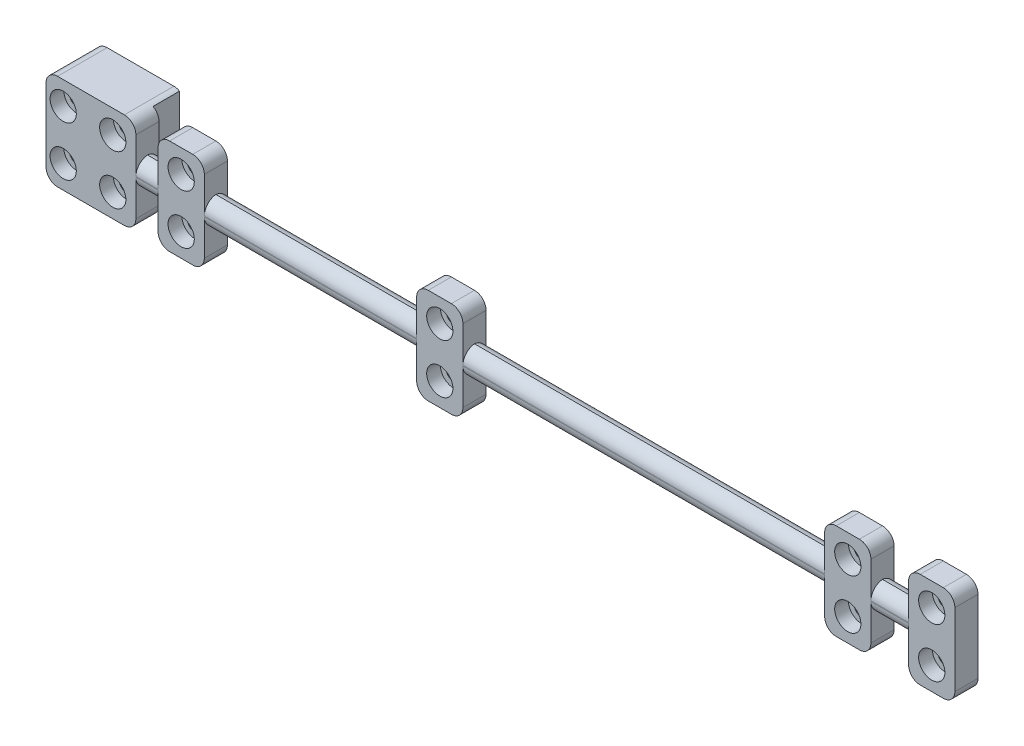
SolidWorks part; units mm, degrees
ref_plane "Front Plane" through (0, 0, 0) normal (0, 0, 1) x (1, 0, 0)
ref_plane "Top Plane" through (0, 0, 0) normal (0, 1, 0) x (1, 0, 0)
ref_plane "Right Plane" through (0, 0, 0) normal (1, 0, 0) x (0, 0, -1)
sketch "Sketch1" plane through (0, 0, 0) normal (0, 0, 1) x (1, 0, 0)
  line L1 (-12.7, -14.5) -> (12.7, -14.5)
  line L2 (-12.7, -14.5) -> (-12.7, 14.5)
  line L3 (-12.7, 14.5) -> (12.7, 14.5)
  line L4 (12.7, -14.5) -> (12.7, 14.5)
  line L5 (-12.7, -14.5) -> (12.7, 14.5) construction
  line L6 (-12.7, 14.5) -> (12.7, -14.5) construction
  line L7 (-7.5, 7.5) -> (7.5, 7.5) construction
  line L8 (-7.5, 7.5) -> (-7.5, -7.5) construction
  line L9 (-7.5, -7.5) -> (7.5, -7.5) construction
  line L10 (7.5, 7.5) -> (7.5, -7.5) construction
  line L11 (-7.5, 7.5) -> (7.5, -7.5) construction
  line L12 (-7.5, -7.5) -> (7.5, 7.5) construction
  point P0 (0, 0)
  point P6 (0, 0)
  dimension "D1" = 29
  dimension "D2" = 25.4
  dimension "D3" = 15
extrude "Boss-Extrude1" add sketch "Sketch1" along normal blind 8
sketch "Sketch2" plane through (0, 0, 8) normal (0, 0, 1) x (1, 0, 0)
  line L0 (12.7, 14.5) -> (-12.7, 14.5) construction
  line L1 (-12.7, -14.5) -> (262.3, -14.5)
  line L2 (-12.7, -14.5) -> (-12.7, 14.5)
  line L3 (-12.7, 14.5) -> (262.3, 14.5)
  line L4 (262.3, -14.5) -> (262.3, 14.5)
  dimension "D1" = 275
extrude "Boss-Extrude2" add sketch "Sketch2" along normal blind 7
sketch "Sketch3" plane through (0, 0, 15) normal (0, 0, 1) x (1, 0, 0)
  line L0 (7.5, 0) -> (28.2, 0) construction
  line L1 (-7.5, 7.5) -> (7.5, 7.5) construction
  line L2 (-7.5, 7.5) -> (-7.5, -7.5) construction
  line L3 (-7.5, -7.5) -> (7.5, -7.5) construction
  line L4 (7.5, 7.5) -> (7.5, -7.5) construction
  line L5 (-7.5, 7.5) -> (7.5, -7.5) construction
  line L6 (-7.5, -7.5) -> (7.5, 7.5) construction
  line L7 (28.2, 0) -> (106.45, 0) construction
  line L8 (28.2, 0) -> (28.2, -7.5) construction
  line L9 (28.2, 0) -> (28.2, 7.5) construction
  line L10 (106.45, 7.5) -> (106.45, 0) construction
  line L11 (106.45, 0) -> (106.45, -7.5) construction
  line L12 (106.45, 0) -> (229.9, 0) construction
  line L13 (229.9, 0) -> (255.3, 0) construction
  line L14 (229.9, 7.5) -> (229.9, 0) construction
  line L15 (229.9, 0) -> (229.9, -7.5) construction
  line L16 (255.3, 7.5) -> (255.3, 0) construction
  line L17 (255.3, 0) -> (255.3, -7.5) construction
  line L18 (255.3, 0) -> (262.3, 0) construction
  line L19 (262.3, -14.5) -> (262.3, 14.5) construction
  point P0 (0, 0)
  point P7 (-7.5, 7.5)
  point P8 (-7.5, -7.5)
  point P9 (7.5, -7.5)
  point P10 (7.5, 7.5)
  point P18 (28.2, -7.5)
  point P19 (28.2, 7.5)
  point P20 (106.45, -7.5)
  point P21 (106.45, 7.5)
  point P28 (229.9, 7.5)
  point P29 (229.9, -7.5)
  point P30 (255.3, 7.5)
  point P31 (255.3, -7.5)
  dimension "D1" = 15
  dimension "D2" = 20.7
  dimension "D3" = 78.25
  dimension "D4" = 25.4
  dimension "D5" = 7
hole_wizard "CBORE for #8 Socket Head Cap Screw1" positions "3DSketch2" profile "Sketch4" counterbore size "#8" standard "ANSI Inch"
sketch3d "3DSketch2"
  point P0 (-7.5, 7.5, 15)
  point P3 (7.5, 7.5, 15)
  point P6 (7.5, -7.5, 15)
  point P9 (-7.5, -7.5, 15)
  point P12 (28.2, 7.5, 15)
  point P15 (28.2, -7.5, 15)
  point P18 (106.45, 7.5, 15)
  point P21 (106.45, -7.5, 15)
  point P24 (229.9, 7.5, 15)
  point P27 (229.9, -7.5, 15)
  point P30 (255.3, 7.5, 15)
  point P33 (255.3, -7.5, 15)
sketch "Sketch4" plane through (-7.5, 7.5, 15) normal (1, 0, 0) x (0, -1, 0)
  line L0 (0, 0) -> (0, 20)
  line L1 (0, 20) -> (2.2479, 18.6493)
  line L2 (2.2479, 18.6493) -> (2.2479, 4.1656)
  line L3 (2.2479, 4.1656) -> (3.9688, 4.1656)
  line L4 (3.9688, 4.1656) -> (3.9688, 0)
  line L5 (3.9688, 0) -> (0, 0)
  line L10 (0, 20) -> (-2.2479, 18.6493) construction
  line L11 (0, -6.35) -> (0, 107.95) construction
  dimension "Hole Dia." = 4.4958
  dimension "Hole Depth" = 20
  dimension "C'Bore Dia." = 7.9375
  dimension "C'Bore Depth" = 4.1656
  dimension "Drill Angle" = 118
sketch "Sketch5" plane through (0, 0, 15) normal (0, 0, 1) x (1, 0, 0)
  line L0 (262.3, 14.5) -> (-12.7, 14.5) construction
  line L1 (35.2, 14.5) -> (99.45, 14.5)
  line L2 (35.2, 14.5) -> (35.2, 4)
  line L3 (35.2, 4) -> (99.45, 4)
  line L4 (99.45, 14.5) -> (99.45, 4)
  line L5 (28.2, 7.5) -> (35.2, 7.5) construction
  line L6 (113.45, 14.5) -> (222.9, 14.5)
  line L7 (113.45, 14.5) -> (113.45, 4)
  line L8 (113.45, 4) -> (222.9, 4)
  line L9 (222.9, 14.5) -> (222.9, 4)
  line L10 (236.9, 14.5) -> (248.3, 14.5)
  line L11 (236.9, 14.5) -> (236.9, 4)
  line L12 (236.9, 4) -> (248.3, 4)
  line L13 (248.3, 14.5) -> (248.3, 4)
  line L14 (106.45, 7.5) -> (99.45, 7.5) construction
  line L15 (106.45, 7.5) -> (113.45, 7.5) construction
  line L16 (229.9, 7.5) -> (222.9, 7.5) construction
  line L17 (229.9, 7.5) -> (236.9, 7.5) construction
  line L18 (248.3, 7.5) -> (255.3, 7.5) construction
  line L19 (7.5, 7.5) -> (14.5, 7.5) construction
  line L20 (14.5, 14.5) -> (21.2, 14.5)
  line L21 (14.5, 14.5) -> (14.5, 4)
  line L22 (14.5, 4) -> (21.2, 4)
  line L23 (21.2, 14.5) -> (21.2, 4)
  line L24 (28.2, 7.5) -> (21.2, 7.5) construction
  line L25 (28.2, 0) -> (106.45, 0) construction
  dimension "D1" = 7
  dimension "D2" = 4
extrude "Cut-Extrude1" cut sketch "Sketch5" against normal blind 10
mirror "Mirror1" about plane through (0, 0, 0) normal (0, 1, 0) of "Cut-Extrude1"
fillet "Fillet1" radius 3.9 16 edges at (168.175, 4, 15) (242.6, 4, 15) (242.6, 4, 8) (242.6, -4, 15) (242.6, -4, 8) (168.175, -4, 8) (168.175, -4, 15) (168.175, 4, 8) (67.325, 4, 8) (67.325, 4, 15) (67.325, -4, 8) (67.325, -4, 15) (17.85, -4, 8) (17.85, -4, 15) (17.85, 4, 8) (17.85, 4, 15)
fillet "Fillet2" radius 3.5 20 edges at (248.3, 14.5, 11.5) (262.3, 14.5, 11.5) (262.3, -14.5, 11.5) (236.9, 14.5, 11.5) (248.3, -14.5, 11.5) (236.9, -14.5, 11.5) (222.9, -14.5, 11.5) (222.9, 14.5, 11.5) (99.45, 14.5, 11.5) (113.45, 14.5, 11.5) (113.45, -14.5, 11.5) (99.45, -14.5, 11.5) (21.2, -14.5, 11.5) (35.2, -14.5, 11.5) (21.2, 14.5, 11.5) (35.2, 14.5, 11.5) (14.5, 14.5, 11.5) (-12.7, 14.5, 7.5) (14.5, -14.5, 11.5) (-12.7, -14.5, 7.5)
